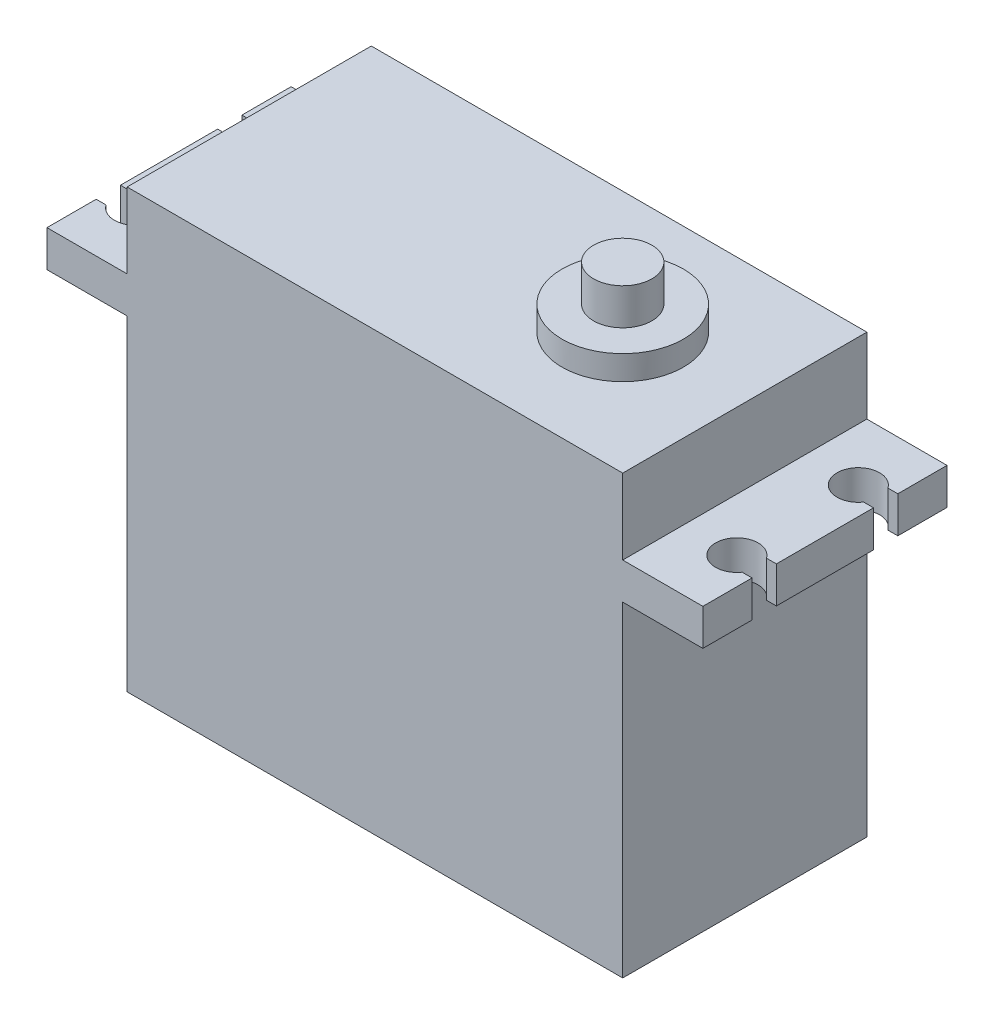
SolidWorks part; units mm, degrees
ref_plane "Front Plane" through (0, 0, 0) normal (0, 0, 1) x (1, 0, 0)
ref_plane "Top Plane" through (0, 0, 0) normal (0, 1, 0) x (1, 0, 0)
ref_plane "Right Plane" through (0, 0, 0) normal (1, 0, 0) x (0, 0, -1)
sketch "Sketch2" plane through (0, 0, 0) normal (0, 1, 0) x (1, 0, 0)
  line L0 (0, 0) -> (0, 10.05) construction
  line L1 (0, 0) -> (10.05, 0) construction
  line L2 (0, 0) -> (0, -10.05) construction
  line L3 (0, 0) -> (-30.75, 0) construction
  line L4 (-35.1, 5) -> (-35.1, -5) construction
  line L5 (-30.75, 10.05) -> (10.05, 10.05)
  line L6 (-30.75, 10.05) -> (-30.75, -10.05)
  line L7 (-30.75, -10.05) -> (10.05, -10.05)
  line L8 (10.05, 10.05) -> (10.05, -10.05)
  line L9 (-30.75, 10.05) -> (-37.35, 10.05) construction
  line L10 (-37.35, 10.05) -> (-37.35, -10.05) construction
  line L11 (-37.35, -10.05) -> (-30.75, -10.05) construction
  line L12 (-10.35, 10.05) -> (-10.35, -10.05) construction
  line L13 (14.4, 5) -> (14.4, -5) construction
  line L14 (-36.85, 5) -> (-37.35, 5) construction
  line L15 (10.05, 10.05) -> (16.65, 10.05) construction
  line L16 (16.65, 10.05) -> (16.65, -10.05) construction
  line L17 (16.65, -10.05) -> (10.05, -10.05) construction
  circle A0 centre (0, 0) radius 2.4
  circle A1 centre (0, 0) radius 10.05 construction
  circle A2 centre (-35.1, 5) radius 1.75
  circle A3 centre (-35.1, -5) radius 1.75
  circle A4 centre (14.4, -5) radius 1.75
  circle A5 centre (14.4, 5) radius 1.75
  circle A6 centre (0, 0) radius 5 construction
  dimension "D1" = 4.8
  dimension "D6" = 3.5
  dimension "D8" = 10
  dimension "D2" = 40.8
  dimension "D3" = 20.1
  dimension "D4" = 10
  dimension "D5" = 49.5
  dimension "D7" = 0.5
sketch "Sketch3" plane through (0, 0, 0) normal (0, 0, 1) x (1, 0, 0)
  line L0 (-30.75, 0) -> (-30.75, 26.8)
  line L1 (-30.75, 26.8) -> (-37.35, 26.8)
  line L2 (-37.35, 26.8) -> (-37.35, 29.8)
  line L3 (-37.35, 29.8) -> (-30.75, 29.8)
  line L4 (-30.75, 29.8) -> (-30.75, 36)
  line L5 (-30.75, 36) -> (10.05, 36)
  line L6 (10.05, 36) -> (10.05, 29.8)
  line L7 (10.05, 29.8) -> (16.65, 29.8)
  line L8 (16.65, 29.8) -> (16.65, 26.8)
  line L9 (16.65, 26.8) -> (10.05, 26.8)
  line L10 (10.05, 26.8) -> (10.05, 0)
  line L11 (10.05, 0) -> (-30.75, 0)
  line L12 (-10.35, 0) -> (-10.35, 36) construction
  line L13 (2.4, 0) -> (2.4, 41) construction
  line L14 (2.4, 0) -> (-2.4, 0) construction
  line L15 (2.4, 41) -> (-2.4, 41) construction
  line L16 (-2.4, 41) -> (-2.4, 0) construction
  line L17 (10.05, 0) -> (-10.05, 0) construction
  line L18 (-5, 38) -> (5, 38) construction
  line L19 (-5, 0) -> (-5, 38) construction
  line L20 (5, 38) -> (5, 0) construction
  dimension "D1" = 26.8
  dimension "D2" = 3
  dimension "D3" = 3
  dimension "D4" = 38
  dimension "D5" = 2
extrude "Boss-Extrude1" add sketch "Sketch3" along normal up to vertex (10.05 mm away) from vertex up to point (-30.75, 0, 10.05) starting at point (-30.75, 0, -10.05)
sketch "Sketch4" plane through (0, 29.8, 0) normal (0, 1, 0) x (1, 0, 0)
  line L0 (-10.35, 10.05) -> (-10.35, -10.05) construction
  line L1 (-10.35, 10.05) -> (-10.35, -10.05) construction
  line L2 (-37.35, 10.05) -> (-37.35, -10.05) construction
  line L4 (-37.35, 6) -> (-37.35, 4)
  line L5 (16.65, -6) -> (15.8361, -6)
  line L6 (-10.35, 0) -> (-37.35, 0) construction
  line L7 (-37.35, 4) -> (-36.5361, 4)
  line L8 (-37.35, 6) -> (-36.5361, 6)
  line L9 (-35.1, 5) -> (-37.35, 5) construction
  line L10 (-37.35, -4) -> (-37.35, -6)
  line L11 (-37.35, -4) -> (-36.5361, -4)
  line L12 (-37.35, -6) -> (-36.5361, -6)
  line L13 (16.65, -4) -> (16.65, -6)
  line L14 (16.65, -4) -> (15.8361, -4)
  line L15 (16.65, 4) -> (15.8361, 4)
  line L16 (16.65, 6) -> (16.65, 4)
  line L17 (16.65, 6) -> (15.8361, 6)
  circle A0 centre (-35.1, -5) radius 1.75 construction
  circle A1 centre (-35.1, 5) radius 1.75 construction
  circle A2 centre (14.4, 5) radius 1.75 construction
  circle A3 centre (14.4, -5) radius 1.75 construction
  arc A4 (-36.5361, -6) -> (-36.5361, -4) centre (-35.1, -5) ccw
  arc A5 (-36.5361, 4) -> (-36.5361, 6) centre (-35.1, 5) ccw
  arc A6 (15.8361, 6) -> (15.8361, 4) centre (14.4, 5) ccw
  arc A7 (15.8361, -4) -> (15.8361, -6) centre (14.4, -5) ccw
  dimension "D1" = 2
extrude "Cut-Extrude1" cut sketch "Sketch4" against normal through all
sketch "Sketch5" plane through (0, 36, 0) normal (0, 1, 0) x (1, 0, 0)
  circle A0 centre (0, 0) radius 5 construction
  circle A1 centre (0, 0) radius 5
extrude "Boss-Extrude2" add sketch "Sketch5" along normal up to vertex (2 mm away) up to point (-5, 38, 0)
sketch "Sketch6" plane through (0, 38, 0) normal (0, 1, 0) x (1, 0, 0)
  circle A0 centre (0, 0) radius 2.4 construction
  circle A1 centre (0, 0) radius 2.4
extrude "Boss-Extrude3" add sketch "Sketch6" along normal up to vertex (3 mm away) up to point (-2.4, 41, 0)
sketch "Sketch7" plane through (0, 38, 0) normal (0, 1, 0) x (1, 0, 0)
  circle A0 centre (0, 0) radius 2.25
  dimension "D1" = 4.5
